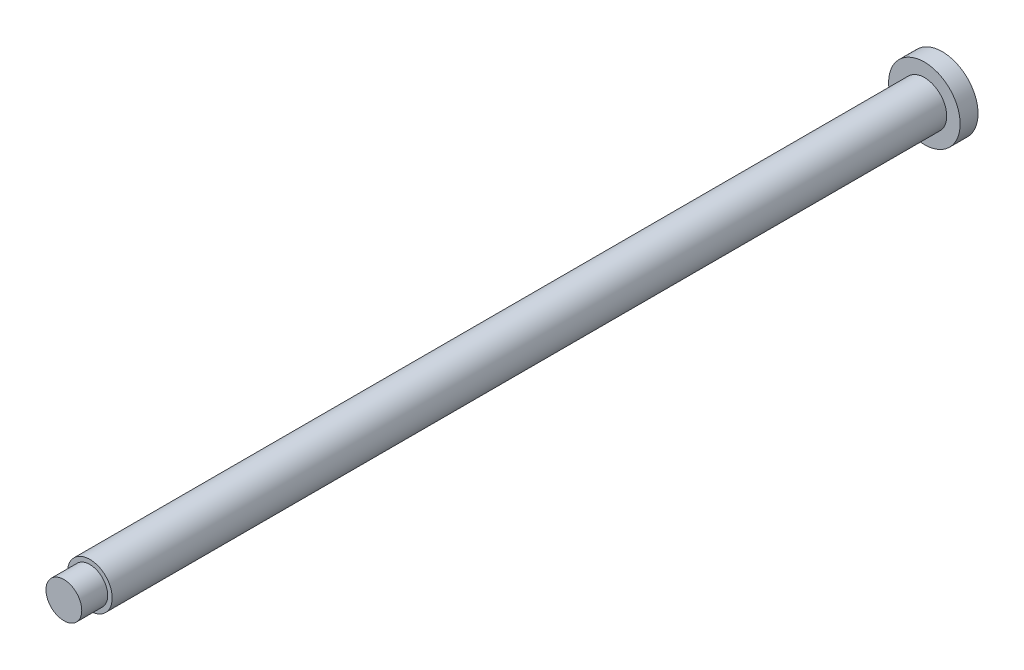
SolidWorks part; units mm, degrees
ref_plane "Front Plane" through (0, 0, 0) normal (1, 0, 0) x (0, 1, 0)
ref_plane "Top Plane" through (0, 0, 0) normal (0, 0, 1) x (0, 1, 0)
ref_plane "Right Plane" through (0, 0, 0) normal (0, 1, 0) x (-1, 0, 0)
sketch "Sketch1" plane through (0, 0, 0) normal (0, 0, 1) x (0, 1, 0)
  circle A0 centre (0, 0) radius 2.5
extrude "Boss-Extrude1" add sketch "Sketch1" along normal blind 93.25 contours A0
sketch "Sketch2" plane through (0, 0, 0) normal (0, 0, -1) x (1, 0, 0)
  circle A0 centre (0, 0) radius 4
extrude "Boss-Extrude2" add sketch "Sketch2" along normal blind 2
sketch "Sketch3" plane through (0, 0, -2) normal (0, 0, -1) x (1, 0, 0)
  circle A0 centre (0, 0) radius 2.05
extrude "Cut-Extrude1" cut sketch "Sketch3" against normal blind 3
sketch "Sketch4" plane through (0, 0, 93.25) normal (0, 0, 1) x (1, 0, 0)
  circle A0 centre (0, 0) radius 2
extrude "Boss-Extrude3" add sketch "Sketch4" along normal blind 2.9
